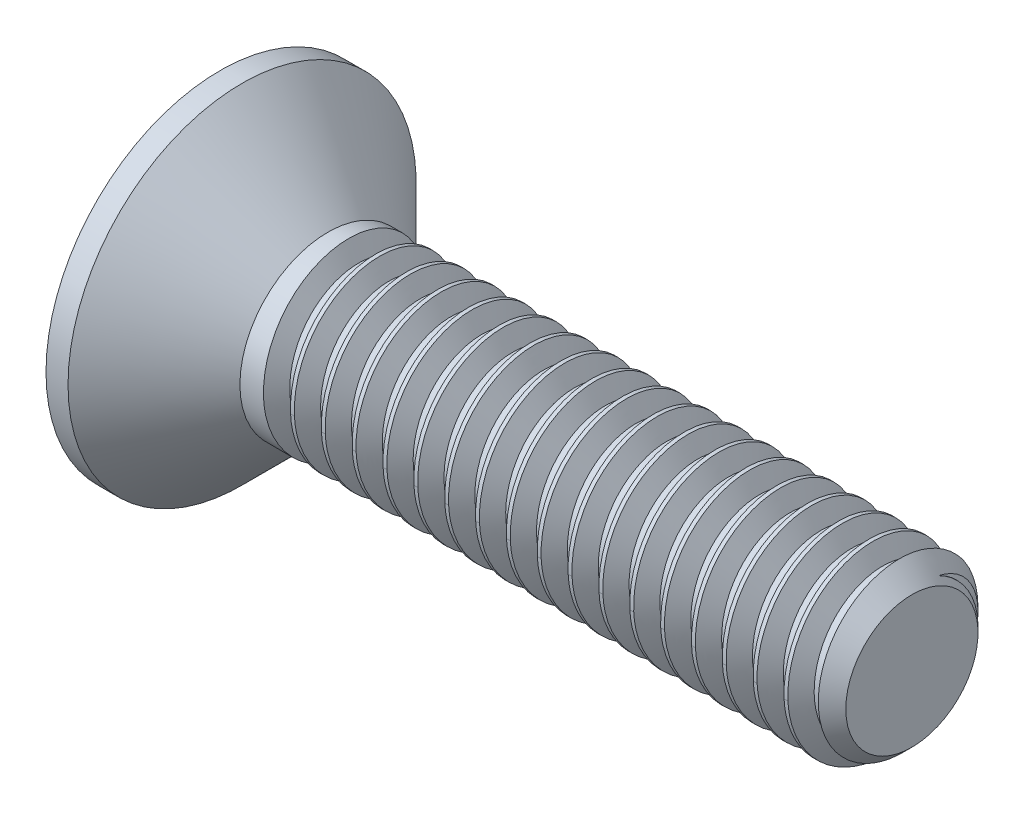
SolidWorks part; units mm, degrees
material "Простая углеродистая сталь"
ref_plane "Front Plane" through (0, 0, 0) normal (0, 0, 1) x (1, 0, 0)
ref_plane "Top Plane" through (0, 0, 0) normal (0, 1, 0) x (1, 0, 0)
ref_plane "Right Plane" through (0, 0, 0) normal (1, 0, 0) x (0, 0, -1)
sketch "Эскиз1" plane through (0, 0, 0) normal (0, 0, 1) x (1, 0, 0)
  line L0 (0, 0) -> (21.128, 0) construction
  line L1 (0, 0) -> (0, 3.95)
  line L3 (2.45, 2) -> (15.7, 2)
  line L4 (15.7, 2) -> (15.7, 0)
  line L5 (15.7, 0) -> (0, 0)
  line L6 (0, 3.95) -> (0.5, 3.95)
  line L7 (0.5, 3.95) -> (2.45, 2)
  dimension "D1" = 15.7
  dimension "D2" = 7.9
  dimension "D3" = 4
  dimension "D4" = 0.5
  dimension "D5" = 45
revolve "Повернуть1" add sketch "Эскиз1" angle 360 about L0
chamfer "Фаска1" distance 0.5 angle 45 1 edges at (15.7, 0, 2)
thread "Резьба1" pitch 0.7 method cut profile "Профиль резьбы1" start angle 0, offset 1, length 13, pitch 0.7, diameter 4
ref_plane "Плоскость1" through (16.2, 0, 2) normal (0, -1, 0) x (0, 0, 1)
sketch "Профиль резьбы1" plane through (16.2, 0, 2) normal (0, -1, 0) x (0, 0, 1)
  line L0 (0, 0) -> (0, 0.7) construction
  line L11 (0, 0) -> (0, 0.6125)
  line L12 (0, 0.6125) -> (-0.3789, 0.3937)
  line L13 (-0.3789, 0.3937) -> (-0.3789, 0.2187)
  line L15 (-0.3789, 0.2187) -> (0, 0)
  line L17 (-0.3789, 0.3062) -> (0, 0.3062) construction
  point P2 (0, 0)
  dimension "Pitch" = 0.7
  dimension "Profile_Angle" = 60
  dimension "Profile_Land" = 0.175
  dimension "Profile_Height" = 0.3789
sketch "Эскиз5" plane through (0, 0, 0) normal (-1, 0, 0) x (0, 0, 1)
  line L1 (1.5011, 0) -> (0.7506, 1.3)
  line L2 (0.7506, 1.3) -> (-0.7506, 1.3)
  line L3 (-0.7506, 1.3) -> (-1.5011, 0)
  line L4 (-1.5011, 0) -> (-0.7506, -1.3)
  line L5 (-0.7506, -1.3) -> (0.7506, -1.3)
  line L6 (0.7506, -1.3) -> (1.5011, 0)
  circle A0 centre (0, 0) radius 1.3 construction
  dimension "D1" = 2.6
extrude "Вырез-Вытянуть1" cut sketch "Эскиз5" against normal blind 2.2
